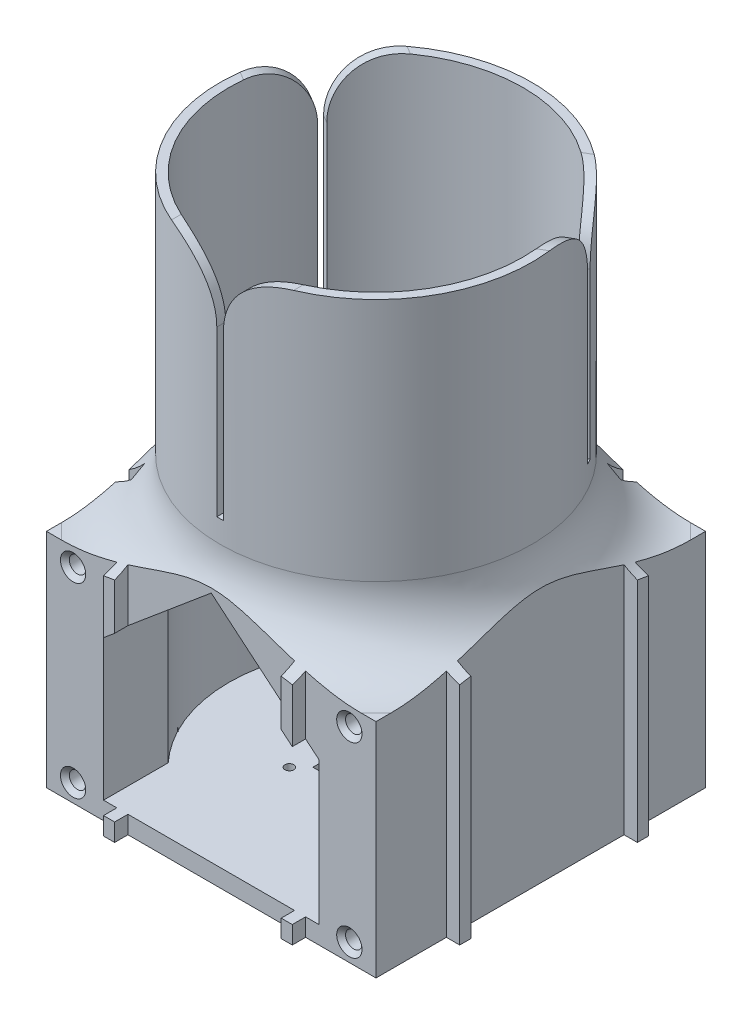
SolidWorks part; units mm, degrees
ref_plane "Front Plane" through (0, 0, 0) normal (0, 0, 1) x (1, 0, 0)
ref_plane "Top Plane" through (0, 0, 0) normal (0, 1, 0) x (1, 0, 0)
ref_plane "Right Plane" through (0, 0, 0) normal (1, 0, 0) x (0, 0, -1)
sketch "Sketch1" plane through (0, 0, 0) normal (0, 1, 0) x (1, 0, 0)
  line L0 (7.1, -7.1) -> (7.1, 7.1)
  line L1 (7.1, -7.1) -> (-7.1, -7.1)
  line L2 (7.1, 7.1) -> (-7.1, 7.1)
  line L3 (-7.1, -7.1) -> (-7.1, 7.1)
  line L4 (7.1, -7.1) -> (-7.1, 7.1) construction
  line L5 (7.1, 7.1) -> (-7.1, -7.1) construction
  line L6 (37.1, -37.1) -> (37.1, -21.25)
  line L7 (37.1, -37.1) -> (21.25, -37.1)
  line L8 (37.1, 37.1) -> (21.5, 37.1)
  line L9 (-37.1, -37.1) -> (-37.1, -21.5)
  line L10 (37.1, -37.1) -> (-37.1, 37.1) construction
  line L11 (37.1, 37.1) -> (-37.1, -37.1) construction
  line L12 (37.1, 21.25) -> (40.1, 21.25)
  line L13 (40.1, 21.25) -> (40.1, 18.75)
  line L14 (40.1, 18.75) -> (37.1, 18.75)
  line L15 (21.25, 0) -> (30.6436, 0) construction
  line L16 (40.1, -18.75) -> (37.1, -18.75)
  line L17 (40.1, -21.25) -> (40.1, -18.75)
  line L18 (37.1, -21.25) -> (40.1, -21.25)
  line L19 (37.1, 21.25) -> (37.1, 37.1)
  line L20 (37.1, -18.75) -> (37.1, 18.75)
  line L21 (21.25, -37.1) -> (21.25, -40.1)
  line L22 (21.25, -40.1) -> (18.75, -40.1)
  line L23 (18.75, -40.1) -> (18.75, -37.1)
  line L24 (18.75, -37.1) -> (-18.75, -37.1)
  line L25 (-37.1, -18.5) -> (-33.6, -18.5)
  line L26 (-33.6, -18.5) -> (-33.6, -21.5)
  line L27 (-33.6, -21.5) -> (-37.1, -21.5)
  line L28 (21.5, 37.1) -> (21.5, 33.6)
  line L29 (21.5, 33.6) -> (18.5, 33.6)
  line L30 (18.5, 33.6) -> (18.5, 37.1)
  line L31 (18.5, 37.1) -> (-18.5, 37.1)
  line L32 (-37.1, -18.5) -> (-37.1, 18.5)
  line L33 (-33.6, 21.5) -> (-37.1, 21.5)
  line L34 (-33.6, 18.5) -> (-33.6, 21.5)
  line L35 (-37.1, 18.5) -> (-33.6, 18.5)
  line L36 (-37.1, 21.5) -> (-37.1, 37.1)
  line L37 (0, 0) -> (0, 18.7785) construction
  line L38 (-18.75, -40.1) -> (-18.75, -37.1)
  line L39 (-21.25, -40.1) -> (-18.75, -40.1)
  line L40 (-21.25, -37.1) -> (-21.25, -40.1)
  line L41 (-21.5, 37.1) -> (-21.5, 33.6)
  line L42 (-21.5, 33.6) -> (-18.5, 33.6)
  line L43 (-18.5, 33.6) -> (-18.5, 37.1)
  line L44 (-21.25, -37.1) -> (-37.1, -37.1)
  line L45 (-21.5, 37.1) -> (-37.1, 37.1)
  circle A0 centre (0, 0) radius 33.1
  circle A2 centre (-9.751, 9.751) radius 1
  circle A3 centre (9.751, 9.751) radius 1
  circle A4 centre (9.751, -9.751) radius 1
  circle A5 centre (-9.751, -9.751) radius 1
  point P1 (0, 0)
  point P2 (0, 0)
  point P34 (0, 0)
  point P36 (20, -40.1)
  point P38 (40.1, -20)
  point P50 (40.1, 20)
  point P51 (-33.6, 20)
  point P53 (20, 33.6)
  dimension "D3" = 66.2
  dimension "D8" = 2
  dimension "D1" = 14.2
  dimension "D2" = 4
  dimension "D4" = 2.5
  dimension "D6" = 3
  dimension "D7" = 13.79
  dimension "D10" = 20
  dimension "D11" = 3
  dimension "D12" = 3.5
  dimension "D13" = 4
  dimension "D5" = 20
  dimension "D9" = 4
extrude "Boss-Extrude1" add sketch "Sketch1" along normal blind 4 contours L16 L20 L14 L13 L12 L19 L8 L9 L7 L6 L18 L17 A0 | A0 L1 L3 L2 L0 region at (29.175, 0, 36.0082) region at (-32.1638, 0, 0)
extrude "Boss-Extrude2" add sketch "Sketch1<4>" along normal blind 50 contours L16 L20 L14 L13 L12 L19 L8 L9 L7 L6 L18 L17 A0 region at (29.175, 0, 36.0082)
sketch "Sketch1<4>" plane through (0, 0, 0) normal (0, 1, 0) x (1, 0, 0) same geometry as "Sketch1"
sketch "Sketch12" plane through (0, 50, 0) normal (0, 1, 0) x (1, 0, 0)
  circle A0 centre (0, 0) radius 33.1
  circle A1 centre (0, 0) radius 35.1
  dimension "D1" = 66.2
  dimension "D2" = 2
extrude "Boss-Extrude3" add sketch "Sketch12" along normal blind 70
fillet "Fillet2" radius 15 1 edges at (0, 50, 35.1)
sketch "Sketch9" plane through (0, 120, 0) normal (0, 1, 0) x (1, 0, 0)
  line L0 (0, 0) -> (37.922, 21.8943) construction
  line L1 (0, 0) -> (0, -43.7885) construction
  line L2 (0, 0) -> (-37.922, 21.8943) construction
  line L3 (0.75, -0.433) -> (0.75, -43.7885)
  line L4 (-0.75, -0.433) -> (-38.297, 21.2447)
  line L5 (0, 0.866) -> (37.547, 22.5438)
  line L6 (-0.75, -0.433) -> (-0.75, -43.7885)
  line L7 (0, 0.866) -> (-37.547, 22.5438)
  line L8 (0.75, -0.433) -> (38.297, 21.2447)
  line L9 (-37.547, 22.5438) -> (-38.297, 21.2447)
  line L10 (37.547, 22.5438) -> (38.297, 21.2447)
  line L11 (-0.75, -43.7885) -> (0.75, -43.7885)
  line L12 (-0.375, 0.6495) -> (37.547, 22.5438) construction
  line L13 (0.375, 0.6495) -> (-37.547, 22.5438) construction
  line L14 (0.75, 0) -> (0.75, -43.7885) construction
  line L15 (0.375, -0.6495) -> (38.297, 21.2447) construction
  line L16 (-0.375, -0.6495) -> (-38.297, 21.2447) construction
  line L17 (-0.75, 0) -> (-0.75, -43.7885) construction
  dimension "D1" = 120
  dimension "D2" = 120
  dimension "D3" = 1.5
extrude "Cut-Extrude2" cut sketch "Sketch9" against normal blind 50 and the other way blind 50
sketch "Sketch13" plane through (0, 0, -37.1) normal (0, 0, -1) x (-1, 0, 0)
  line L0 (-37.1, 51.9215) -> (-37.1, 0) construction
  line L1 (-37.1, 0) -> (-21.5, 0) construction
  line L2 (-33.669, 50) -> (-37.1, 50) construction
  line L3 (37.1, 50) -> (37.1, 0) construction
  line L4 (33.6, 0) -> (33.6, 28.0835) construction
  line L5 (21.5, 0) -> (37.1, 0) construction
  circle A0 centre (-31.1, 4) radius 1.85
  circle A1 centre (31.1, 4) radius 1.85
  circle A2 centre (31.1, 46) radius 1.85
  circle A3 centre (-31.1, 46) radius 1.85
  dimension "D1" = 3.7
  dimension "D2" = 6
  dimension "D3" = 4
  dimension "D4" = 4
  dimension "D5" = 6
  dimension "D6" = 3.5
extrude "Cut-Extrude3" cut sketch "Sketch13" against normal blind 22
ref_plane "Plane1" through (0, 0, 0) normal (0, 0, -1) x (-1, 0, 0)
mirror "Mirror3" about plane through (0, 0, 0) normal (0, 0, -1) of "Cut-Extrude3"
chamfer "Chamfer1" distance 1 angle 45 8 edges at (29.25, 46, -37.1) (29.25, 4, -37.1) (-32.95, 46, -37.1) (-32.95, 4, -37.1) (29.25, 4, 37.1) (29.25, 46, 37.1) (-32.95, 46, 37.1) (-32.95, 4, 37.1)
sketch "Sketch14" plane through (0, 0, -37.1) normal (0, 0, -1) x (-1, 0, 0)
  line L0 (0, 0) -> (0, 57.5167) construction
  line L3 (24.25, 36.1685) -> (0, 56.5167)
  line L4 (-24.25, 36.1685) -> (0, 56.5167)
  line L8 (24.25, 36.1685) -> (24.25, 4)
  line L9 (24.25, 4) -> (-24.25, 4)
  line L10 (-24.25, 4) -> (-24.25, 36.1685)
  line L11 (-24.25, 36.1685) -> (0, 36.1685) construction
  line L12 (-18.5, 0) -> (18.5, 0) construction
  circle A1 centre (-31.1, 4) radius 2.85 construction
  spline S0 degree 3 poles (18.5, 52.7406) (16.9749, 53.2204) (15.46, 53.7353) (12.4322, 54.7728) (10.9197, 55.2963) (7.8698, 56.2565) (6.3324, 56.6936) (3.9748, 57.1704) (3.1802, 57.299) (1.5673, 57.4738) (0.7658, 57.5178) (-0.8263, 57.5155) (-1.6169, 57.4694) (-3.1885, 57.2971) (-3.9696, 57.1711) (-6.3017, 56.7005) (-7.845, 56.2638) (-10.904, 55.3017) (-12.4192, 54.7773) (-15.4526, 53.7378) (-16.9705, 53.2218) (-18.5, 52.7406) knots 0 0 0 0 0.125 0.125 0.25 0.25 0.375 0.375 0.4375 0.4375 0.5 0.5 0.5625 0.5625 0.625 0.625 0.75 0.75 0.875 0.875 1 1 1 1 construction
  dimension "D4" = 4
  dimension "D1" = 40
  dimension "D2" = 4
  dimension "D3" = 1
extrude "Cut-Extrude4" cut sketch "Sketch14" against normal blind 177
fillet "Fillet3" radius 10 2 edges at (-24.25, 36.1685, -29.8144) (24.25, 36.1685, -29.8144)
fillet "Fillet5" radius 13 6 edges at (-29.8993, 120, -16.3964) (-29.1493, 120, -17.6954) (29.1493, 120, -17.6954) (29.8993, 120, -16.3964) (0.75, 120, 34.0917) (-0.75, 120, 34.0917)
equation "\"CanDiameter\"=40.6328"
equation "\"D11@Sketch1\"=\"D4@Sketch1\"+.5"
equation "\"D12@Sketch1\"=\"D6@Sketch1\"+.5"
equation "\"D5@Sketch1\"=\"D10@Sketch1\""
